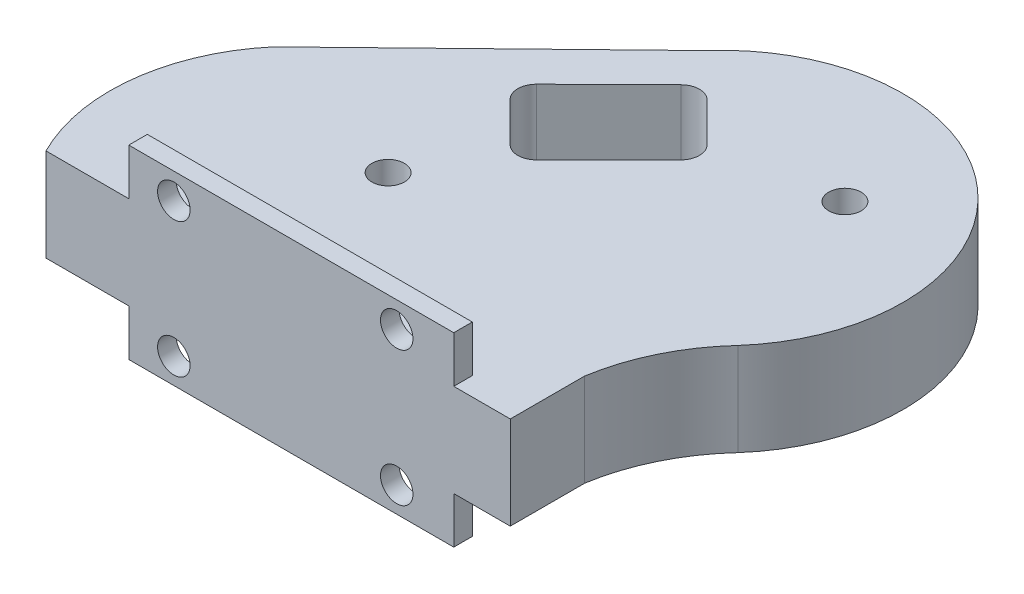
SolidWorks part; units mm, degrees
ref_plane "Front Plane" through (0, 0, 0) normal (0, 0, 1) x (1, 0, 0)
ref_plane "Top Plane" through (0, 0, 0) normal (0, 1, 0) x (1, 0, 0)
ref_plane "Right Plane" through (0, 0, 0) normal (1, 0, 0) x (0, 0, -1)
sketch "Sketch1" plane through (0, 0, 0) normal (0, 1, 0) x (1, 0, 0)
  line L0 (0, 0) -> (50, 0)
  line L1 (2.5356, 21.9463) -> (26.2158, 44.9299)
  line L2 (50, 0) -> (50, 8)
  arc A0 (0, 0) -> (2.5356, 21.9463) centre (17.8501, 9.0572) cw
  arc A1 (26.2158, 44.9299) -> (55.3976, 19.1107) centre (40.8067, 32.0203) cw
  arc A4 (50, 8) -> (55.3976, 19.1107) centre (71.1751, 4.5796) cw
  dimension "D1" = 50
  dimension "D2" = 33
extrude "Boss-Extrude1" add sketch "Sketch1" along normal blind 10
sketch "Sketch2" plane through (0, 0, 0) normal (0, 0, 1) x (1, 0, 0)
  line L0 (26.2158, 0) -> (60.2888, 0) construction
  line L1 (0, 5) -> (-11.7674, 5) construction
  line L2 (8.913, -5) -> (43.913, -5)
  line L3 (8.913, -5) -> (8.913, 0)
  line L4 (8.913, 0) -> (43.913, 0)
  line L5 (43.913, -5) -> (43.913, 0)
  line L6 (0, 10) -> (0, 0) construction
  line L7 (8.913, 10) -> (43.913, 10)
  line L8 (43.913, 15) -> (43.913, 10)
  line L9 (8.913, 15) -> (43.913, 15)
  line L10 (8.913, 15) -> (8.913, 10)
  dimension "D1" = 35
  dimension "D2" = 5
extrude "Boss-Extrude2" add sketch "Sketch2" against normal blind 2
sketch "Sketch3" plane through (0, 0, -2) normal (0, 0, -1) x (-1, 0, 0)
  circle A0 centre (-13.7694, -2.2635) radius 1.75
  circle A1 centre (-37.7694, -2.2635) radius 1.75
  circle A2 centre (-37.7694, 12.2365) radius 1.75
  circle A3 centre (-13.7694, 12.2365) radius 1.75
  dimension "D1" = 2
  dimension "D2" = 2
extrude "Cut-Extrude1" cut sketch "Sketch3" against normal blind 2
sketch "Sketch5" plane through (0, 10, 0) normal (0, 1, 0) x (1, 0, 0)
  circle A0 centre (20.4485, 16.3927) radius 1.75
  circle A1 centre (47.741, 38.3042) radius 1.75
  dimension "D1" = 35
extrude "Cut-Extrude4" cut sketch "Sketch5" against normal blind 9
sketch "Sketch6" plane through (0, 10, 0) normal (0, 1, 0) x (1, 0, 0)
  line L0 (18.7594, 31.2251) -> (29.4348, 41.7624)
  line L5 (29.4348, 41.7624) -> (36.4368, 34.7604)
  line L6 (36.4368, 34.7604) -> (25.8305, 24.154)
  line L7 (25.8305, 24.154) -> (18.7594, 31.2251)
  dimension "D1" = 15
  dimension "D2" = 10
extrude "Cut-Extrude5" cut sketch "Sketch6" against normal up to surface (10 mm away) up to face at (29.8592, 0, -11.3356)
fillet "Fillet1" radius 2 4 edges at (36.4368, 5, -34.7604) (25.8305, 5, -24.154) (18.7594, 5, -31.2251) (29.4348, 5, -41.7624)
